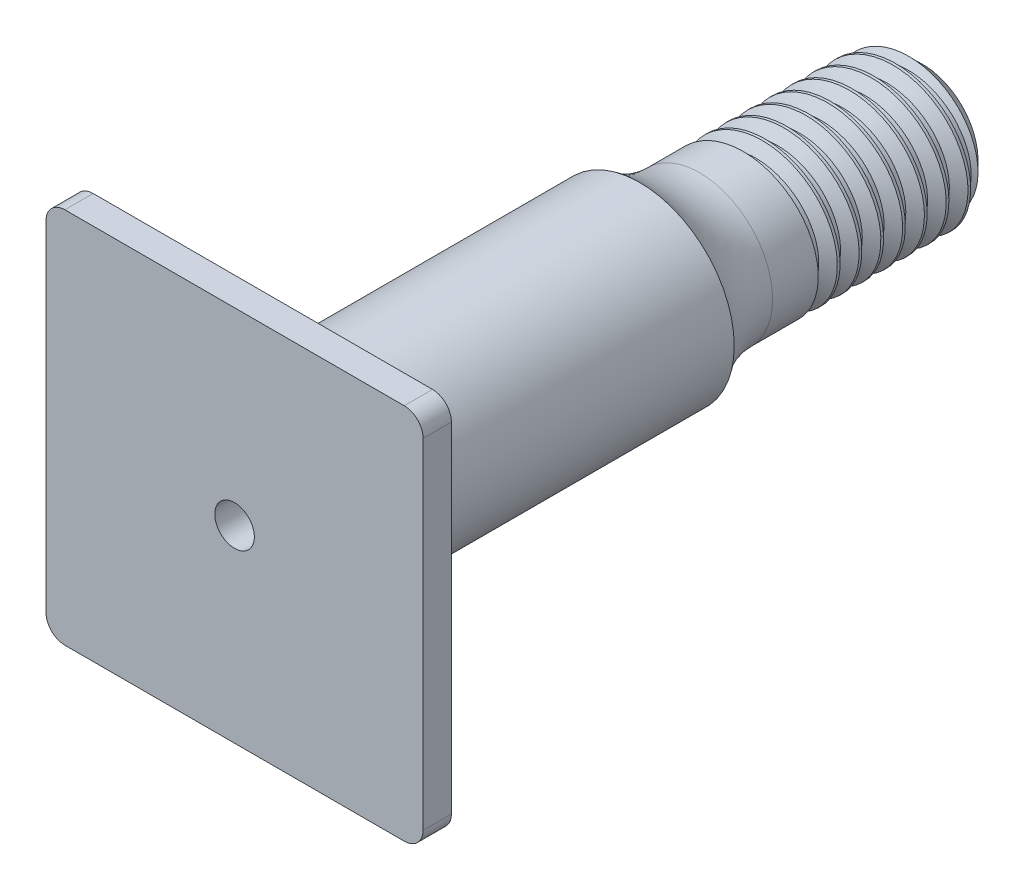
SolidWorks part; units mm, degrees
ref_plane "Front Plane" through (0, 0, 0) normal (0, 0, 1) x (1, 0, 0)
ref_plane "Top Plane" through (0, 0, 0) normal (0, 1, 0) x (1, 0, 0)
ref_plane "Right Plane" through (0, 0, 0) normal (1, 0, 0) x (0, 0, -1)
sketch "Sketch1" plane through (0, 0, 0) normal (0, 0, 1) x (1, 0, 0)
  circle A1 centre (0, 0) radius 10
  dimension "D1" = 20
extrude "Boss-Extrude1" add sketch "Sketch1" along normal blind 40
sketch "Sketch2" plane through (0, 0, 0) normal (0, 0, -1) x (-1, 0, 0)
  circle A0 centre (0, 0) radius 7.75
  dimension "D1" = 15.5
extrude "Boss-Extrude2" add sketch "Sketch2" along normal blind 30
thread "Thread1" pitch 2.3091 method cut profile "Thread Profile1" start angle 0, offset 10, length 20, pitch 2.3091, diameter 15.5
ref_plane "Plane1" through (-7.75, 0, -10) normal (0, -1, 0) x (-1, 0, 0)
sketch "Thread Profile1" plane through (-7.75, 0, -10) normal (0, -1, 0) x (-1, 0, 0)
  line L0 (0, 0) -> (0, 2.3091) construction
  line L11 (0, 0) -> (0, 2.0205)
  line L12 (0, 2.0205) -> (-1.2498, 1.2989)
  line L13 (-1.2498, 1.2989) -> (-1.2498, 0.7216)
  line L15 (-1.2498, 0.7216) -> (0, 0)
  line L17 (-1.2498, 1.0102) -> (0, 1.0102) construction
  point P2 (0, 0)
  dimension "Pitch" = 2.3091
  dimension "Profile_Angle" = 60
  dimension "Profile_Land" = 0.5773
  dimension "Profile_Height" = 1.2498
sketch "Sketch5" plane through (0, 0, 0) normal (1, 0, 0) x (0, 0, -1)
  line L0 (27.4, 8.4567) -> (30, 5.8567)
  line L1 (30, 5.8567) -> (30, 8.4567)
  line L2 (30, 8.4567) -> (27.4, 8.4567)
  line L3 (30, -6.5803) -> (30, -6.5757) construction
  line L4 (-5, 0) -> (34.2291, 0) construction
  dimension "D1" = 2.6
revolve "Cut-Revolve1" cut sketch "Sketch5" angle 360 about L4
fillet "Fillet1" radius 10 1 edges at (-7.75, 0, 0)
sketch "Sketch6" plane through (0, 0, 40) normal (0, 0, 1) x (1, 0, 0)
  line L1 (-20, 20) -> (20, 20)
  line L2 (-20, 20) -> (-20, -20)
  line L3 (-20, -20) -> (20, -20)
  line L4 (20, 20) -> (20, -20)
  line L5 (-20, 20) -> (20, -20) construction
  line L6 (-20, -20) -> (20, 20) construction
  point P0 (0, 0)
  dimension "D1" = 40
  dimension "D2" = 40
extrude "Boss-Extrude3" add sketch "Sketch6" along normal blind 3
fillet "Fillet2" radius 10 1 edges at (10, 0, 40)
fillet "Fillet3" radius 2 4 edges at (-20, -20, 41.5) (20, -20, 41.5) (20, 20, 41.5) (-20, 20, 41.5)
sketch "Sketch7" plane through (0, 0, 0) normal (0, 1, 0) x (1, 0, 0)
  line L0 (0, -30) -> (0, -40) construction
  line L1 (10, -30) -> (-10, -30) construction
  line L2 (0, -40) -> (-18, -40) construction
  line L3 (-3.75, -40) -> (3.75, -40)
  line L4 (-3.75, -40) -> (-3.75, -36.5)
  line L5 (-3.75, -36.5) -> (3.75, -36.5)
  line L6 (3.75, -40) -> (3.75, -36.5)
  line L7 (-3.75, -40) -> (3.75, -36.5) construction
  line L8 (-3.75, -36.5) -> (3.75, -40) construction
  point P5 (0, -38.25)
  dimension "D1" = 7.5
  dimension "D2" = 3.5
extrude "Cut-Extrude1" cut sketch "Sketch7" against normal blind 4.5 and the other way blind 20
sketch "Sketch8" plane through (0, 0, 43) normal (0, 0, 1) x (1, 0, 0)
  circle A0 centre (0, 0) radius 2.1
  dimension "D1" = 4.2
extrude "Cut-Extrude2" cut sketch "Sketch8" against normal blind 15
